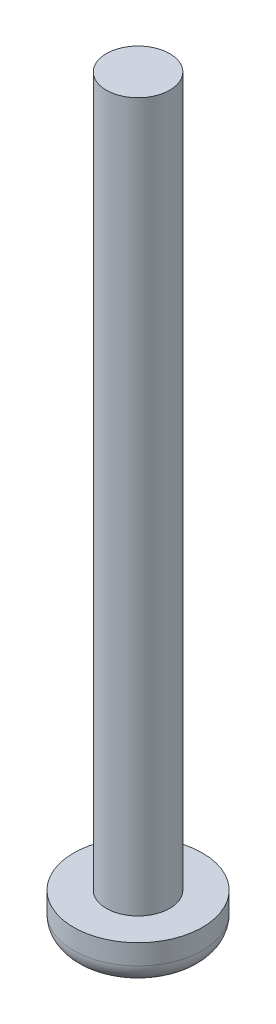
SolidWorks part; units mm, degrees
ref_plane "Front Plane" through (0, 0, 0) normal (0, 0, 1) x (1, 0, 0)
ref_plane "Top Plane" through (0, 0, 0) normal (0, 1, 0) x (1, 0, 0)
ref_plane "Right Plane" through (0, 0, 0) normal (1, 0, 0) x (0, 0, -1)
sketch "Sketch1" plane through (0, 0, 0) normal (0, 1, 0) x (1, 0, 0)
  circle A0 centre (0, 0) radius 1.25
  dimension "D1" = 2.5
extrude "Boss-Extrude1" add sketch "Sketch1" along normal blind 27.94
sketch "Sketch2" plane through (0, 0, 0) normal (0, -1, 0) x (1, 0, 0)
  circle A0 centre (0, 0) radius 2.54
  dimension "D1" = 5.08
extrude "Boss-Extrude2" add sketch "Sketch2" along normal blind 1.5875
sketch "Sketch3" plane through (0, -1.5875, 0) normal (0, -1, 0) x (1, 0, 0)
  line L0 (-1.7859, 0.1984) -> (-1.7859, -0.1984)
  line L1 (-1.7859, -0.1984) -> (-0.1984, -0.1984)
  line L2 (-0.1984, -0.1984) -> (-0.1984, -1.7859)
  line L3 (-0.1984, -1.7859) -> (0.1984, -1.7859)
  line L4 (0.1984, -1.7859) -> (0.1984, -0.1984)
  line L5 (0.1984, -0.1984) -> (1.7859, -0.1984)
  line L6 (1.7859, -0.1984) -> (1.7859, 0.1984)
  line L7 (1.7859, 0.1984) -> (0.1984, 0.1984)
  line L8 (0.1984, 0.1984) -> (0.1984, 1.7859)
  line L9 (0.1984, 1.7859) -> (-0.1984, 1.7859)
  line L10 (-0.1984, 1.7859) -> (-0.1984, 0.1984)
  line L11 (-0.1984, 0.1984) -> (-1.7859, 0.1984)
  line L12 (-0.1984, 0.1984) -> (0.1984, -0.1984) construction
  line L13 (0.1984, 0.1984) -> (-0.1984, -0.1984) construction
  dimension "D1" = 0.3969
  dimension "D2" = 1.5875
extrude "Cut-Extrude1" cut sketch "Sketch3" against normal blind 0.7937
fillet "Fillet1" radius 0.7937 1 edges at (0, -1.5875, -2.54)
fillet "Fillet2" radius 0.0496 44 edges at (-0.9922, -0.7937, 0.1984) (-0.9667, -1.5875, 0.1984) (-1.7859, -0.7937, 0) (-1.7859, -1.1898, 0.1984) (-0.9922, -0.7937, -0.1984) (-0.9667, -1.5875, -0.1984) (-1.7859, -1.1898, -0.1984) (0, -0.7937, -1.7859) (-0.1984, -1.1906, -0.1984) (-0.1984, -0.7937, -0.9922) (-0.1984, -1.1898, -1.7859) (-0.1984, -1.5875, -0.9667) (0.1984, -0.7937, -0.9922) (0.1984, -1.5875, -0.9667) (0.1984, -1.1898, -1.7859) (0.1984, -1.1906, -0.1984) (0.9922, -0.7937, -0.1984) (0.9667, -1.5875, -0.1984) (1.7859, -0.7937, 0) (1.7859, -1.1898, -0.1984) (0.9922, -0.7937, 0.1984) (0.9667, -1.5875, 0.1984) (1.7859, -1.1898, 0.1984) (0.1984, -1.1906, 0.1984) (0.1984, -0.7937, 0.9922) (0.1984, -1.5875, 0.9667) (0, -0.7937, 1.7859) (0.1984, -1.1898, 1.7859) (-0.1984, -0.7937, 0.9922) (-0.1984, -1.1906, 0.1984) (-0.1984, -1.5875, 0.9667) (-0.1984, -1.1898, 1.7859)
